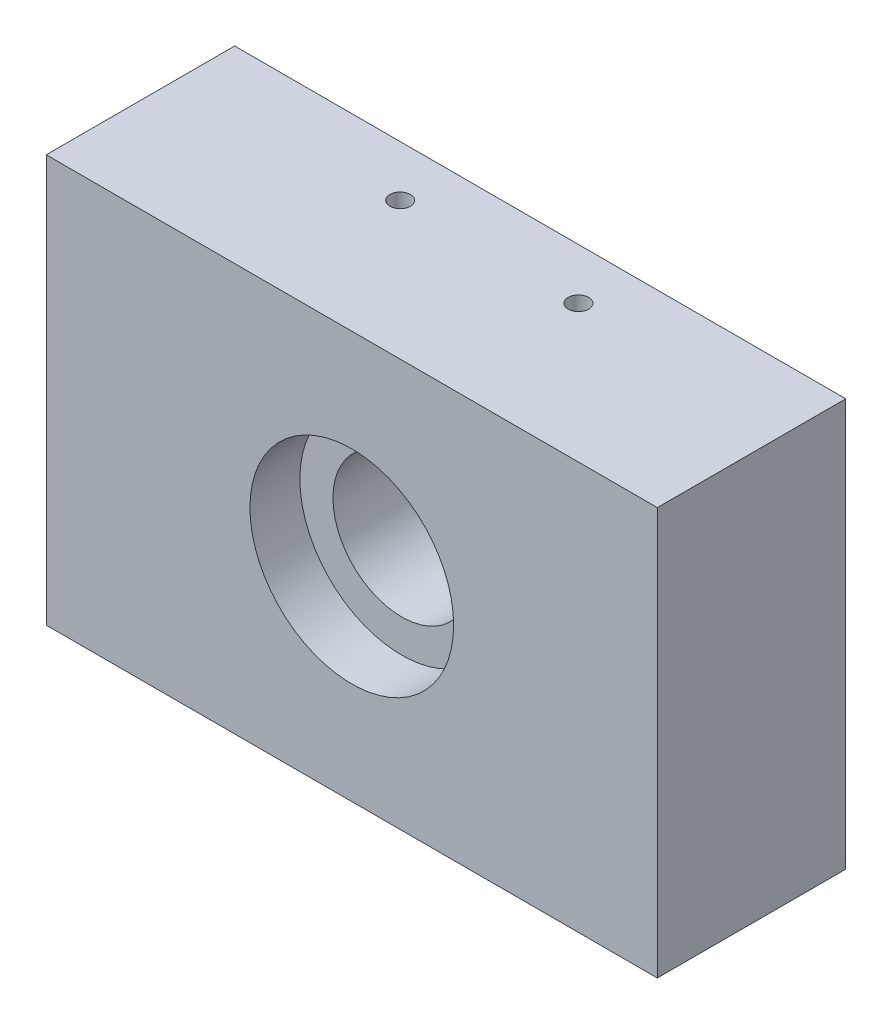
SolidWorks part; units mm, degrees
material "1060 Alloy"
ref_plane "Front Plane" through (0, 0, 0) normal (0, 0, 1) x (1, 0, 0)
ref_plane "Top Plane" through (0, 0, 0) normal (0, 1, 0) x (1, 0, 0)
ref_plane "Right Plane" through (0, 0, 0) normal (1, 0, 0) x (0, 0, -1)
sketch "Sketch1" plane through (0, 0, 0) normal (0, 0, 1) x (1, 0, 0)
  line L1 (0, 0) -> (152.4, 0)
  line L2 (0, 0) -> (0, 101.6)
  line L3 (0, 101.6) -> (152.4, 101.6)
  line L4 (152.4, 0) -> (152.4, 101.6)
  dimension "D1" = 152.4
  dimension "D2" = 101.6
extrude "Boss-Extrude1" add sketch "Sketch1" along normal blind 46.99
sketch "Sketch2" plane through (0, 0, 0) normal (0, 0, -1) x (-1, 0, 0)
  line L0 (0, 50.8) -> (-152.4, 50.8) construction
  line L1 (0, 101.6) -> (0, 0) construction
  line L2 (-152.4, 0) -> (-152.4, 101.6) construction
  line L4 (-152.4, 101.6) -> (0, 101.6) construction
  line L5 (-76.2, 101.6) -> (-76.2, 0) construction
  line L6 (0, 0) -> (-152.4, 0) construction
  circle A0 centre (-76.2, 50.8) radius 25.4
  circle A1 centre (-76.2, 50.8) radius 17.145
  dimension "D1" = 50.8
  dimension "D2" = 34.29
extrude "Cut-Extrude1" cut sketch "Sketch2" against normal through all contours A1
extrude "Cut-Extrude3" cut sketch "Sketch2<2>" against normal blind 12.446
sketch "Sketch2<2>" plane through (0, 0, 0) normal (0, 0, -1) x (-1, 0, 0) same geometry as "Sketch2"
ref_plane "Plane2" through (0, 0, 23.495) normal (0, 0, -1) x (-1, 0, 0)
mirror "Mirror2" about plane through (0, 0, 23.495) normal (0, 0, -1) of "Cut-Extrude3"
hole_wizard "Tap Drill for 1/2-13 Tap1" positions "Sketch4" profile "Sketch5" hole size "1/2-13" standard "ANSI Inch"
sketch "Sketch4" plane through (0, 0, 0) normal (0, -1, 0) x (-1, 0, 0)
  line L0 (55.88, -23.495) -> (-55.88, -23.495) construction
  line L2 (-76.2, -46.99) -> (-76.2, 0) construction
  line L3 (0, -46.99) -> (-152.4, -46.99) construction
  line L4 (0, 0) -> (-152.4, 0) construction
  point P0 (-68.0517, -23.495)
  point P4 (-29.9517, -23.495)
  dimension "D1" = 46.2483
  dimension "D2" = 38.1
sketch "Sketch5" plane through (68.0517, 0, 23.495) normal (1, 0, 0) x (0, 0, -1)
  line L0 (0, 0) -> (0, 22.2695)
  line L1 (0, 22.2695) -> (5.3581, 19.05)
  line L2 (5.3581, 19.05) -> (5.3581, 0)
  line L5 (5.3581, 0) -> (0, 0)
  line L10 (0, 22.2695) -> (-5.3581, 19.05) construction
  line L11 (0, -6.35) -> (0, 107.95) construction
  dimension "Hole Dia." = 10.7163
  dimension "Hole Depth" = 19.05
  dimension "Drill Angle" = 118
hole_wizard "Tap Drill for 1/4-20 Tap1" positions "Sketch7" profile "Sketch8" hole size "1/4-20" standard "ANSI Inch"
sketch "Sketch7" plane through (50.8, 101.6, 0) normal (0, -1, 0) x (0, 0, -1)
  line L3 (0, 101.6) -> (0, -50.8) construction
  line L4 (-46.99, -50.8) -> (0, -50.8) construction
  point P0 (-12.7, 47.625)
  point P2 (-12.7, 3.175)
  point P14 (-12.7, 0.0327)
  dimension "D1" = 12.7
  dimension "D2" = 12.7
  dimension "D3" = 44.45
  dimension "D4" = 53.975
sketch "Sketch8" plane through (98.425, 101.6, 12.7) normal (1, 0, 0) x (0, 0, 1)
  line L0 (0, 0) -> (0, 15.24)
  line L1 (0, 15.24) -> (2.5527, 13.7062)
  line L2 (2.5527, 13.7062) -> (2.5527, 0)
  line L5 (2.5527, 0) -> (0, 0)
  line L10 (0, 15.24) -> (-2.5527, 13.7062) construction
  line L11 (0, -6.35) -> (0, 107.95) construction
  dimension "Hole Dia." = 5.1054
  dimension "Hole Depth" = 15.24
  dimension "Drill Angle" = 118
equation "\"through_diamiter\"= 1.35"
equation "\"D2@Sketch2\"= \"through_diamiter\""
equation "\"bearing depth\"= 0.5"
equation "\"hole spacing\"= 0.75"
equation "\"D1@Sketch4\" = \"hole spacing\"+\"center_distance\""
equation "\"center_distance\"= 1.07080043"
